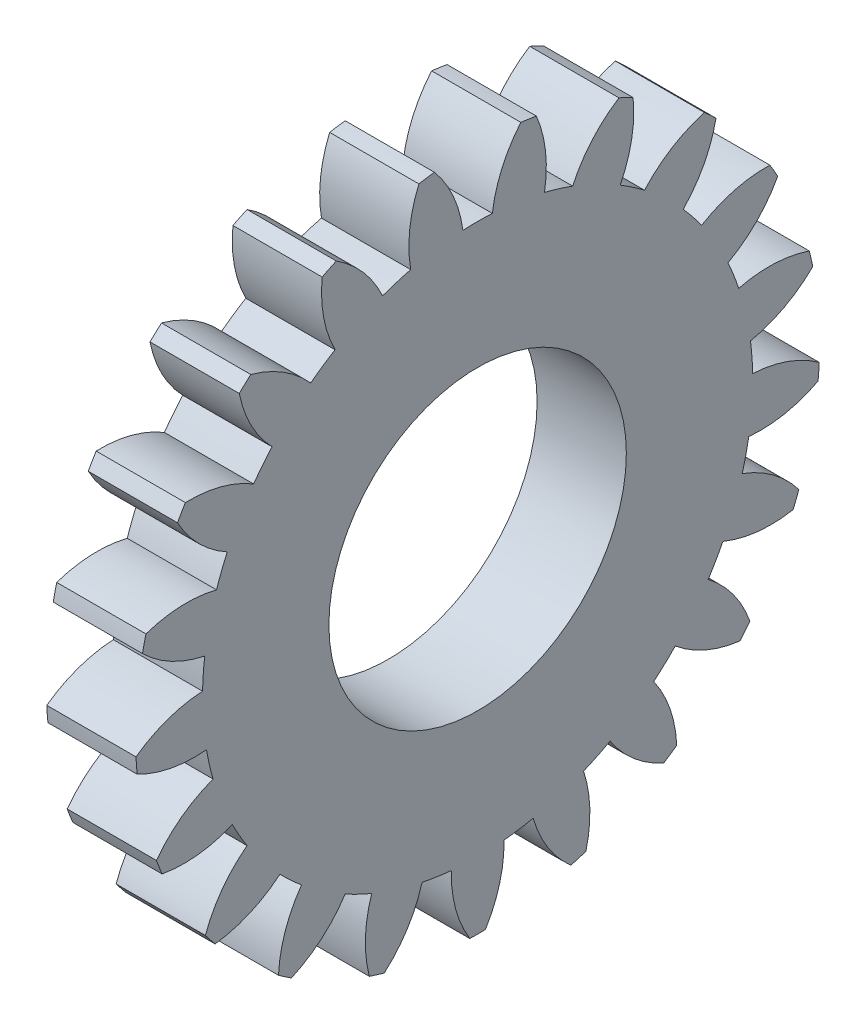
SolidWorks part; units mm, degrees
material "ﾎﾟﾘｵｷｼﾒﾁﾚﾝ(POM)ｱｾﾀｰﾙ共重合体"
ref_plane "Plane1" through (0, 0, 0) normal (0, 0, 1) x (1, 0, 0)
ref_plane "Plane2" through (0, 0, 0) normal (0, 1, 0) x (1, 0, 0)
ref_plane "Plane3" through (0, 0, 0) normal (1, 0, 0) x (0, 0, -1)
other "Configuration Table"
sketch "HoldingSke" plane through (0, 0, 0) normal (0, 1, 0) x (1, 0, 0)
  line L0 (0, 0) -> (0.9336, -0.3584)
  line L1 (-15, 0) -> (100, 0) construction
  line L2 (0, 0) -> (-2.1039, 2.3779)
  line L3 (0, 0) -> (-11.863, 4.5341)
  line L4 (0, 0) -> (8.0624, 3.0949)
  line L5 (0, 0) -> (-46.8476, -17.4728)
  line L6 (0, 0) -> (-2.4869, -1.6779)
  line L7 (-2.1039, 2.3779) -> (8.6586, 51.2059)
  line L8 (-76.2, 54.61) -> (-75.2, 54.61)
  line L9 (-71.009, 38.7566) -> (-53.1078, 45.2721)
  line L10 (-76.2, 71.12) -> (104.1128, 71.12)
  line L11 (0, 0) -> (-3, 0)
  line L12 (-76.2, 101.6) -> (-76.162, 101.6)
  line L13 (24.9733, 27.94) -> (52.9518, 28.4284)
  line L14 (24.9733, 27.94) -> (24.9743, 27.94)
  line L15 (24.9733, 27.94) -> (100.4006, 29.5858)
  line L16 (-63.627, -1) -> (-12.827, -1)
  circle A0 centre (0, 0) radius 4
  circle A1 centre (0, 0) radius 9.249
  circle A2 centre (0, 0) radius 37.5
  circle A3 centre (0, 0) radius 4
  dimension "MHD" = 18.498
  dimension "Hub_dia" = 75
  dimension "Bore" = 8
  dimension "MBD" = 8
  dimension "Num_teeth" = 21
  dimension "Pitch" = 1
  dimension "Overall_len" = 50
  dimension "Show_teeth" = 21
  dimension "Thickness" = 3
  dimension "OAL" = 50.0001
  dimension "T_dim" = 1
  dimension "Ap" = 20
  dimension "H" = 19.05
  dimension "Pitch_radius" = 180.3128
  dimension "Width" = 3
  dimension "Backlash" = 0.038
  dimension "Addendum_fac" = 1
  dimension "Dedendum_fac" = 1.25
  dimension "Clearance_fac" = 0.25
  dimension "Dedendum_add" = 0.001
  dimension "Module" = 1
sketch "BasProSke" plane through (0, 0, 0) normal (0, 1, 0) x (1, 0, 0)
  line L0 (-10, 0) -> (60, 0) construction
  line L1 (0, 0) -> (0, 11.5)
  line L2 (0, 0) -> (3, 0)
  line L3 (3, 0) -> (3, 11.5)
  line L4 (3, 11.5) -> (0, 11.5)
  dimension "Thickness" = 3
  dimension "Diameter" = 23
revolve "Base-Revolve" add sketch "BasProSke" angle 360 about L0
sketch "TooCutSke" plane through (0, 0, 0) normal (1, 0, 0) x (0, 0, -1)
  line L1 (0, 0) -> (0, 107) construction
  line L2 (0, 0) -> (-0.8511, 10.4654) construction
  line L3 (0, 0) -> (-3.1226, 20.7168) construction
  line L4 (-0.8511, 10.4654) -> (-1.5613, 10.3584) construction
  arc A0 (0.4953, 9.2357) -> (-0.4953, 9.2357) centre (0, 0) ccw
  arc A1 (1.4725, 11.431) -> (-1.4725, 11.431) centre (0, 0) ccw
  circle A2 centre (0, 0) radius 10.5 construction
  circle A3 centre (0, 0) radius 9.8668 construction
  arc A4 (-0.4953, 9.2357) -> (-1.4725, 11.431) centre (-4.6605, 8.6967) ccw
  arc A5 (1.4725, 11.431) -> (0.4953, 9.2357) centre (4.6605, 8.6967) ccw
  dimension "Root_dia" = 18.498
  dimension "Overcut_dia" = 23.0508
  dimension "Pitch_dia" = 21
  dimension "Base_dia" = 19.7335
  dimension "Flank_rad" = 4.2
  dimension "Half_ang" = 8.571
  dimension "Half_CT" = 0.7182
extrude "ToothCut" cut sketch "TooCutSke" along normal through all
fillet "Breaks" [suppressed] radius 0.02 tangent propagation no
fillet "RootFillets" [suppressed] radius 0.251
pattern_circular "TeethCuts" count 21 every 17.143 about axis through (-10, 0, 0) along (1, 0, 0) of "ToothCut", "RootFillets", "Breaks"
sketch "HubNeaOneSke" plane through (0, 0, 0) normal (-1, 0, 0) x (0, 0, 1)
  circle A0 centre (0, 0) radius 9.249
  dimension "Diameter" = 18.498
extrude "HubNearOne" [suppressed] add sketch "HubNeaOneSke" along normal blind 47.0001
sketch "HubNeaBotSke" plane through (0, 0, 0) normal (-1, 0, 0) x (0, 0, 1)
  circle A0 centre (0, 0) radius 9.249
  dimension "Diameter" = 18.498
extrude "HubNearBoth" [suppressed] add sketch "HubNeaBotSke" along normal blind 23.5
ref_plane "FarPln" through (3, 0, 0) normal (1, 0, 0) x (0, 0, -1)
sketch "HubFarSke" plane through (3, 0, 0) normal (1, 0, 0) x (0, 0, -1)
  circle A0 centre (0, 0) radius 9.249
  dimension "Diameter" = 18.498
extrude "HubFar" [suppressed] add sketch "HubFarSke" along normal blind 23.5
sketch "BorSke" plane through (0, 0, 0) normal (1, 0, 0) x (0, 0, -1)
  circle A0 centre (0, 0) radius 4
  dimension "Diameter" = 8
extrude "Bore" cut sketch "BorSke" along normal mid plane 100.0001
sketch "KeySke" plane through (0, 0, 0) normal (1, 0, 0) x (0, 0, -1)
  line L0 (-1, 0) -> (-1, 5)
  line L1 (-1, 5) -> (1, 5)
  line L2 (1, 5) -> (1, 0)
  line L3 (0, 0) -> (0, 34) construction
  line L4 (-1, 0) -> (1, 0)
  dimension "Offset" = 5
  dimension "Width" = 2
extrude "Keyway" [suppressed] cut sketch "KeySke" along normal mid plane 100.0001
pattern_circular "Keyway2" [suppressed] count 2 every 90 about axis through (-10, 0, 0) along (1, 0, 0) reverse direction yes
sketch "ｽｹｯﾁ1" plane through (0, 0, 0) normal (-1, 0, 0) x (0, 0, 1)
  circle A0 centre (0, 0) radius 4 construction
  circle A1 centre (0, 0) radius 4
extrude "ﾎﾞｽ - 押し出し1" add sketch "ｽｹｯﾁ1" against normal up to surface (3 mm away) up to face at (3, 0, 4)
sketch "ｽｹｯﾁ2" plane through (3, 0, 0) normal (1, 0, 0) x (0, 0, -1)
  circle A0 centre (0, 0) radius 5
  point P23 (0, 0)
  dimension "D3" = 10
extrude "ｶｯﾄ - 押し出し1" cut sketch "ｽｹｯﾁ2" against normal through all
equation "' \"Module@HoldingSke\" = 6.35"
equation "' \"Num_teeth@HoldingSke\" = 12"
equation "' \"Ap@HoldingSke\" =  20"
equation "' \"Ap@HoldingSke\" = 20"
equation "' \"Width@HoldingSke\" = 0.5 * 25.4"
equation "' \"Hub_dia@HoldingSke\"= 1 * 25.4"
equation "' \"Hub_dia@HoldingSke\" = 1 * 25.4"
equation "' \"Overall_len@HoldingSke\" = 1.0 * 25.4"
equation "' \"Bore@HoldingSke\" = 0.75 * 25.4"
equation "' \"T_dim@HoldingSke\" = 0.1 * 25.4"
equation "' \"Width@KeySke\" = 0.25 * 25.4"
equation "' \"Show_teeth@HoldingSke\" = 13"
equation "' \"Backlash@HoldingSke\" = 0.009 * 25.4"
equation "' \"Addendum_fac@HoldingSke\" = 1.0"
equation "' \"Dedendum_fac@HoldingSke\" = 1.25"
equation "' \"Dedendum_add@HoldingSke\" = 0.00005 * 25.4"
equation "' \"Clearance_fac@HoldingSke\" = 0.25"
equation "\"Pitch@HoldingSke\" = 1 / \"Module@HoldingSke\""
equation "\"Overcut_dia@TooCutSke\" = (\"Num_teeth@HoldingSke\" + 2 * \"Addendum_fac@HoldingSke\") / \"Pitch@HoldingSke\" + 0.002 * 25.4"
equation "\"Pitch_dia@TooCutSke\" = \"Num_teeth@HoldingSke\" / \"Pitch@HoldingSke\""
equation "\"Base_dia@TooCutSke\" = \"Num_teeth@HoldingSke\" / \"Pitch@HoldingSke\" * cos((\"Ap@HoldingSke\"  * 3.14159265 / 180))"
equation "\"Root_dia@TooCutSke\" = (\"Num_teeth@HoldingSke\" + 2) / \"Pitch@HoldingSke\" - 2 * (\"Addendum_fac@HoldingSke\" + \"Dedendum_fac@HoldingSke\") / \"Pitch@HoldingSke\" - \"Dedendum_add@HoldingSke\" * 2"
equation "\"Half_ang@TooCutSke\" = 180 / \"Num_teeth@HoldingSke\""
equation "\"Half_CT@TooCutSke\" = \"Num_teeth@HoldingSke\" / \"Pitch@HoldingSke\" * sin((3.14159265 / 2 / \"Num_teeth@HoldingSke\")) / 2 - 7 * \"Backlash@HoldingSke\" / 4"
equation "\"Flank_rad@TooCutSke\" = \"Num_teeth@HoldingSke\" / \"Pitch@HoldingSke\" / 5"
equation "\"Radius@RootFillets\" = \"Clearance_fac@HoldingSke\" / \"Pitch@HoldingSke\" + \"Dedendum_add@HoldingSke\""
equation "\"Break_rad@Breaks\" = 0.02 / \"Pitch@HoldingSke\""
equation "\"Thickness@HoldingSke\" = \"Width@HoldingSke\""
equation "\"OAL@HoldingSke\" = \"Thickness@HoldingSke\""
equation "\"MHD@HoldingSke\" = (\"Num_teeth@HoldingSke\" + 2) / \"Pitch@HoldingSke\" - 2 * (\"Addendum_fac@HoldingSke\" + \"Dedendum_fac@HoldingSke\")  / \"Pitch@HoldingSke\" - \"Dedendum_add@HoldingSke\" * 2"
equation "\"MBD@HoldingSke\" = (\"Num_teeth@HoldingSke\" + 2) / \"Pitch@HoldingSke\" - 2 * (\"Addendum_fac@HoldingSke\" + \"Dedendum_fac@HoldingSke\")  / \"Pitch@HoldingSke\" - \"Dedendum_add@HoldingSke\" * 2 - 0.002 * 25.4"
equation "\"MHD@HoldingSke\" = ((sgn( \"MHD@HoldingSke\" - \"Hub_dia@HoldingSke\" )-1)*( \"MHD@HoldingSke\" - \"Hub_dia@HoldingSke\" ))/-2+ \"Hub_dia@HoldingSke\""
equation "\"MBD@HoldingSke\" = ((sgn( \"MBD@HoldingSke\" - \"Bore@HoldingSke\" )-1)*( \"MBD@HoldingSke\" - \"Bore@HoldingSke\" ))/-2+ \"Bore@HoldingSke\""
equation "\"OAL@HoldingSke\" = ((sgn( \"OAL@HoldingSke\" - \"Overall_len@HoldingSke\" )+1)*( \"OAL@HoldingSke\" - \"Overall_len@HoldingSke\" ))/2 + \"Overall_len@HoldingSke\" + 0.000002 * 25.4"
equation "\"Num_teeth@TeethCuts\" = int( \"Show_teeth@HoldingSke\" ) + 1"
equation "\"Num_teeth@TeethCuts\" = ((sgn( \"Num_teeth@TeethCuts\" - \"Num_teeth@HoldingSke\" )-1)*( \"Num_teeth@TeethCuts\" - \"Num_teeth@HoldingSke\" ))/-2+ \"Num_teeth@HoldingSke\""
equation "\"Num_teeth@TeethCuts\" = ((sgn( \"Num_teeth@TeethCuts\" - 2.0)+1)*( \"Num_teeth@TeethCuts\" - 2.0))/2 +2.0"
equation "\"Angle@TeethCuts\" = 360.0 / \"Num_teeth@HoldingSke\""
equation "\"Diameter@BasProSke\" = (\"Num_teeth@HoldingSke\" + 2 * \"Addendum_fac@HoldingSke\") / \"Pitch@HoldingSke\""
equation "\"Thickness@BasProSke\"  = \"Thickness@HoldingSke\""
equation "' \"Fillet_rad@BasProSke\" =  \"Thickness@HoldingSke\" * 0.05"
equation "' \"Fillet_rad@BasProSke\" = \"Thickness@HoldingSke\" * 0.05"
equation "\"MHD@HoldingSke\" = ((sgn( \"MHD@HoldingSke\" - \"Root_dia@TooCutSke\" )-1)*( \"MHD@HoldingSke\" - \"Root_dia@TooCutSke\" ))/-2+ \"Root_dia@TooCutSke\""
equation "\"Diameter@HubNeaOneSke\" = \"MHD@HoldingSke\""
equation "\"Length@HubNearOne\" = \"OAL@HoldingSke\" - \"Thickness@BasProSke\""
equation "\"Diameter@HubNeaBotSke\" = \"MHD@HoldingSke\""
equation "\"Length@HubNearBoth\" = ( \"OAL@HoldingSke\" - \"Thickness@BasProSke\" ) / 2.0"
equation "\"Thickness@FarPln\" = \"Thickness@BasProSke\""
equation "\"Diameter@HubFarSke\" = \"MHD@HoldingSke\""
equation "\"Length@HubFar\" = ( \"OAL@HoldingSke\" - \"Thickness@BasProSke\" ) / 2.0"
equation "\"Diameter@BorSke\" = \"MBD@HoldingSke\""
equation "\"D1@Bore\" = \"OAL@HoldingSke\" * 2.0"
equation "\"D1@Keyway\" = \"OAL@HoldingSke\" * 2.0"
equation "\"Offset@KeySke\" = \"T_dim@HoldingSke\" + \"MBD@HoldingSke\" / 2.0"
